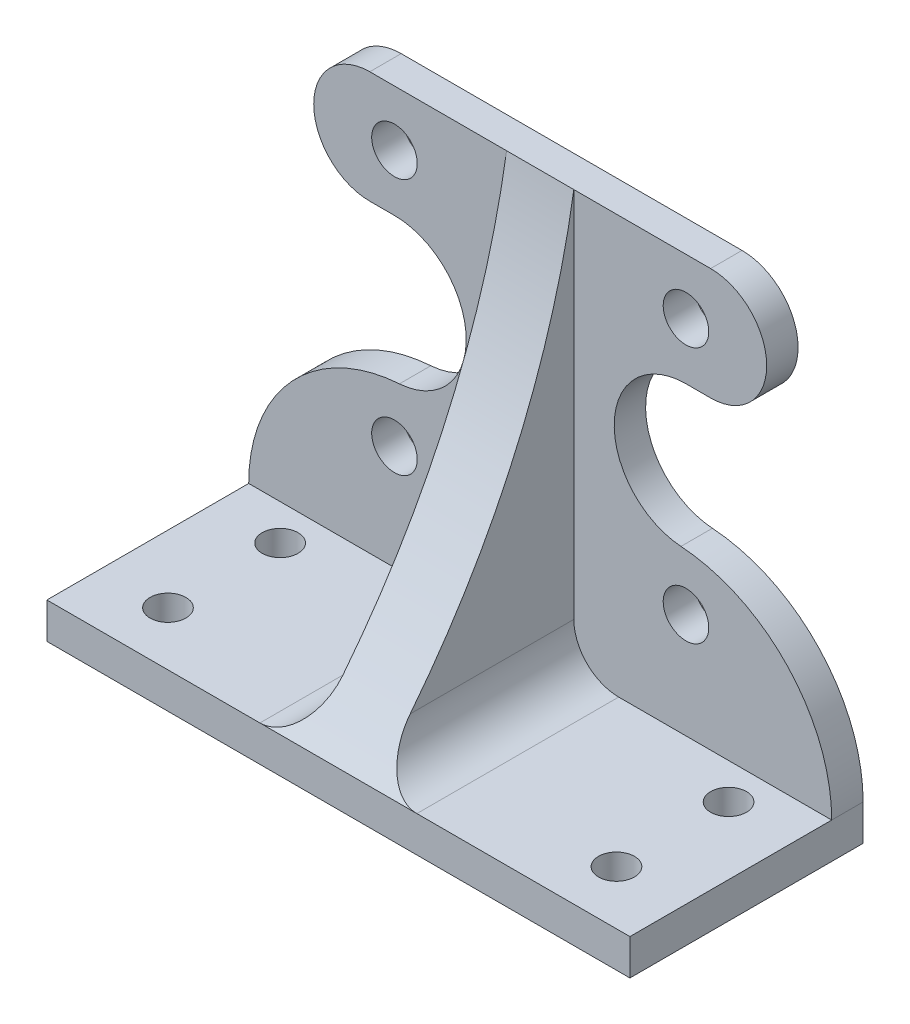
SolidWorks part; units mm, degrees
material "6061-T6 (SS)"
ref_plane "Front Plane" through (0, 0, 0) normal (0, 0, 1) x (1, 0, 0)
ref_plane "Top Plane" through (0, 0, 0) normal (0, 1, 0) x (1, 0, 0)
ref_plane "Right Plane" through (0, 0, 0) normal (1, 0, 0) x (0, 0, -1)
sketch "Sketch1" plane through (0, 0, 0) normal (0, 0, 1) x (1, 0, 0)
  line L1 (-65, 60) -> (65, 60)
  line L2 (-65, 60) -> (-65, -60)
  line L3 (-65, -60) -> (65, -60)
  line L4 (65, 60) -> (65, -60)
  line L5 (-65, 60) -> (65, -60) construction
  line L6 (-65, -60) -> (65, 60) construction
  point P0 (0, 0)
  dimension "D1" = 130
  dimension "D2" = 120
extrude "Boss-Extrude1" add sketch "Sketch1" along normal blind 7
sketch "Sketch2" plane through (0, 0, 7) normal (0, 0, 1) x (1, 0, 0)
  line L0 (-58.2803, 0) -> (70.9633, 0) construction
  line L2 (0, 44.1901) -> (0, -47.0277) construction
  circle A0 centre (-32.5, 0) radius 13.462
  circle A1 centre (-32.5, 28.575) radius 5.08
  circle A2 centre (-32.5, -28.575) radius 5.08
  circle A3 centre (32.5, -28.575) radius 5.08
  circle A4 centre (32.5, 0) radius 13.462
  circle A5 centre (32.5, 28.575) radius 5.08
  dimension "D1" = 26.924
  dimension "D3" = 10.16
  dimension "D2" = 57.15
  dimension "D4" = 32.5
extrude "Cut-Extrude1" cut sketch "Sketch2" against normal through all
sketch "Sketch4" plane through (0, 0, 7) normal (0, 0, 1) x (1, 0, 0)
  line L0 (65, -60) -> (65, 60) construction
  line L1 (-65, -60) -> (65, -60)
  line L2 (-65, -60) -> (-65, -52)
  line L3 (-65, -52) -> (65, -52)
  line L4 (65, -60) -> (65, -52)
  dimension "D1" = 8
extrude "Boss-Extrude2" add sketch "Sketch4" along normal blind 45
sketch "Sketch10" plane through (0, 0, 0) normal (0, 0, -1) x (-1, 0, 0)
  line L0 (65, -60) -> (-65, -60) construction
  line L1 (65, -60) -> (-65, -60)
  line L3 (65, -52) -> (65, -60)
  line L4 (-65, -52) -> (-65, -60)
  line L5 (0, 59.5566) -> (0, -60.8181) construction
  line L6 (-38, 41) -> (38, 41)
  line L8 (-38, 16) -> (-32.5, 16)
  line L9 (38, 16) -> (32.5, 16)
  arc A0 (-32.5, 16) -> (-31.3869, -15.9612) centre (-32.5, 0) cw
  arc A1 (-38, 41) -> (-38, 16) centre (-38, 28.5) ccw
  circle A3 centre (-32.5, 0) radius 13.462 construction
  arc A5 (-31.3869, -15.9612) -> (-65, -52) centre (-28.8737, -52) ccw
  arc A6 (31.3869, -15.9612) -> (65, -52) centre (28.8737, -52) cw
  arc A7 (32.5, 16) -> (31.3869, -15.9612) centre (32.5, 0) ccw
  arc A8 (38, 41) -> (38, 16) centre (38, 28.5) cw
  circle M3 centre (-32.5, 0) radius 13.462
  circle M7 centre (32.5, 0) radius 13.462
  line M8 (-65, 60) -> (-65, -60)
  line M10 (65, -60) -> (65, 60)
  line M11 (65, 60) -> (-65, 60)
  dimension "D1" = 16
  dimension "D2" = 38
  dimension "D3" = 41
extrude "Cut-Extrude4" cut sketch "Sketch10" against normal blind 10 contours L6 A8 L9 A7 A6 A5 A0 L8 A1 M10 M11 M8 M7 M3 region at (-56.5473, -26.189, 0)
sketch "Sketch9" plane through (0, 0, 0) normal (1, 0, 0) x (0, 0, -1)
  line L0 (-7, 41) -> (-52, -52)
sketch "Sketch11" plane through (0, -52, 0) normal (0, 1, 0) x (1, 0, 0)
  line L0 (0, 22.3671) -> (0, -72.0343) construction
  line L1 (-65, 0) -> (65, 0) construction
  line L3 (-65, -52) -> (-65, -7) construction
  circle A0 centre (-50, -15) radius 4
  circle A1 centre (-50, -40) radius 4
  circle A2 centre (50, -40) radius 4
  circle A3 centre (50, -15) radius 4
  dimension "D1" = 8
  dimension "D2" = 15
  dimension "D3" = 25
  dimension "D4" = 15
extrude "Cut-Extrude5" cut sketch "Sketch11" against normal through all
rib "Rib1" sketch "Sketch9" sketch "Sketch9" thickness 15 extrusion direction parallel to sketch draft on no parameters "D1"=15
sketch "Sketch13" plane through (7.5, 0, 0) normal (1, 0, 0) x (0, 0, -1)
  arc A0 (-7, 41) -> (-52, -52) centre (-184.7129, 69.603) cw
  line M1 (-7, 41) -> (-52, -52)
  dimension "D1" = 180
extrude "Cut-Extrude6" cut sketch "Sketch13" against normal through all and the other way through all contours A0 M1 region at (7.5, -6.8216, 26.7687)
fillet "Fillet1" radius 10 2 edges at (7.5, -52, 29.5) (-7.5, -52, 29.5)
sketch "Sketch15" plane through (0, 0, 52) normal (0, 0, 1) x (1, 0, 0)
  line L0 (-65, -60) -> (65, -60) construction
  line L1 (-70.5294, 50) -> (69.4706, 50)
  line L2 (-70.5294, 50) -> (-70.5294, -60)
  line L3 (-70.5294, -60) -> (69.4706, -60)
  line L4 (69.4706, 50) -> (69.4706, -60)
  dimension "D1" = 110
  dimension "D2" = 140
sketch "Sketch16" plane through (0, 0, 0) normal (0, 0, -1) x (-1, 0, 0)
  line L0 (-38, 41) -> (38, 41) construction
  line L1 (-38, 16) -> (-32.5, 16) construction
  line L2 (-65, -60) -> (-65, -52) construction
  line L3 (65, -60) -> (-65, -60) construction
  line L4 (65, -52) -> (65, -60) construction
  line L5 (38, 16) -> (32.5, 16) construction
  line L6 (-38, 41) -> (38, 41)
  line L7 (-38, 16) -> (-32.5, 16)
  line L8 (-65, -60) -> (-65, -52)
  line L9 (65, -60) -> (-65, -60)
  line L10 (65, -52) -> (65, -60)
  line L11 (38, 16) -> (32.5, 16)
  arc A0 (-38, 41) -> (-38, 16) centre (-38, 28.5) ccw construction
  arc A1 (-31.3869, -15.9612) -> (-32.5, 16) centre (-32.5, 0) ccw construction
  arc A2 (-31.3869, -15.9612) -> (-65, -52) centre (-28.8737, -52) ccw construction
  arc A3 (65, -52) -> (31.3869, -15.9612) centre (28.8737, -52) ccw construction
  arc A4 (32.5, 16) -> (31.3869, -15.9612) centre (32.5, 0) ccw construction
  arc A5 (38, 16) -> (38, 41) centre (38, 28.5) ccw construction
  circle A6 centre (32.5, 28.575) radius 5.08 construction
  circle A7 centre (-32.5, 28.575) radius 5.08 construction
  circle A8 centre (-32.5, -28.575) radius 5.08 construction
  circle A9 centre (32.5, -28.575) radius 5.08 construction
  arc A10 (-38, 41) -> (-38, 16) centre (-38, 28.5) ccw
  arc A11 (-31.3869, -15.9612) -> (-32.5, 16) centre (-32.5, 0) ccw
  arc A12 (-31.3869, -15.9612) -> (-65, -52) centre (-28.8737, -52) ccw
  arc A13 (65, -52) -> (31.3869, -15.9612) centre (28.8737, -52) ccw
  arc A14 (32.5, 16) -> (31.3869, -15.9612) centre (32.5, 0) ccw
  arc A15 (38, 16) -> (38, 41) centre (38, 28.5) ccw
  circle A16 centre (32.5, 28.575) radius 5.08
  circle A17 centre (-32.5, 28.575) radius 5.08
  circle A18 centre (-32.5, -28.575) radius 5.08
  circle A19 centre (32.5, -28.575) radius 5.08
equation "\"D4@Sketch2\"=\"D1@Sketch1\"/4"
